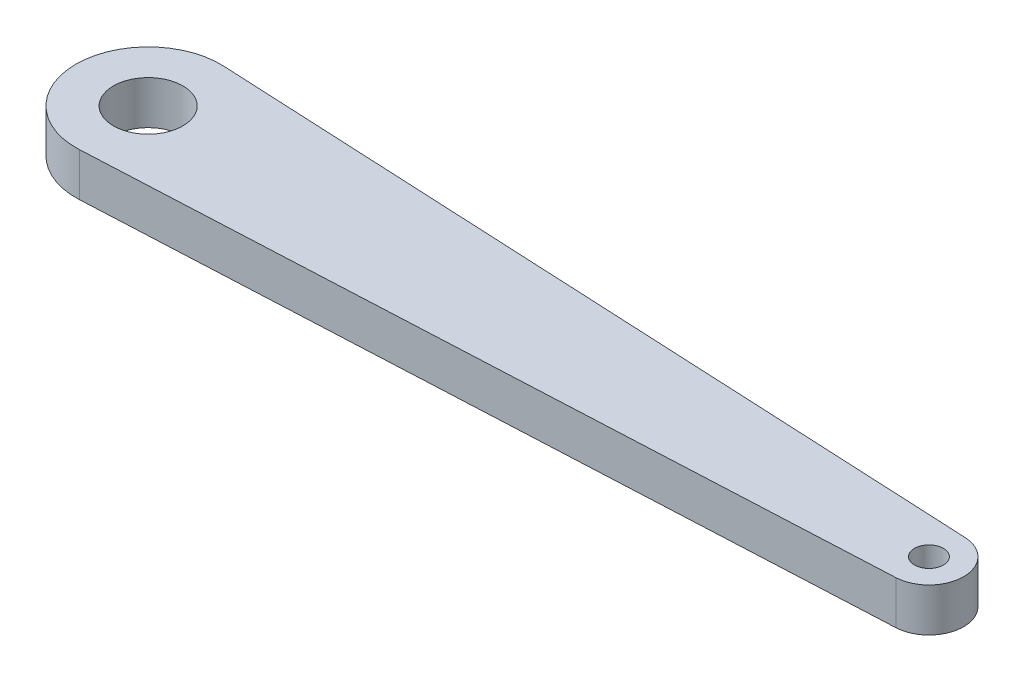
SolidWorks part; units mm, degrees
ref_plane "Front Plane" through (0, 0, 0) normal (0, 0, 1) x (1, 0, 0)
ref_plane "Top Plane" through (0, 0, 0) normal (0, 1, 0) x (1, 0, 0)
ref_plane "Right Plane" through (0, 0, 0) normal (1, 0, 0) x (0, 0, -1)
sketch "Sketch2" plane through (0, 0, 0) normal (0, 1, 0) x (1, 0, 0)
  line L0 (-36.4106, 0) -> (117.0894, 0) construction
  line L1 (-23.3087, 12.4855) -> (111.3783, 5.993)
  line L2 (-23.3087, -12.4855) -> (111.3783, -5.993)
  circle A0 centre (111.0894, 0) radius 2.5
  arc A1 (111.3783, -5.993) -> (111.3783, 5.993) centre (111.0894, 0) ccw
  arc A2 (-23.3087, 12.4855) -> (-23.3087, -12.4855) centre (-23.9106, 0) ccw
  circle A3 centre (-23.9106, 0) radius 6
  dimension "D1" = 12
  dimension "D2" = 5
  dimension "D3" = 25
  dimension "D5" = 12
  dimension "D4" = 135
extrude "Boss-Extrude1" add sketch "Sketch2" along normal blind 7.5
